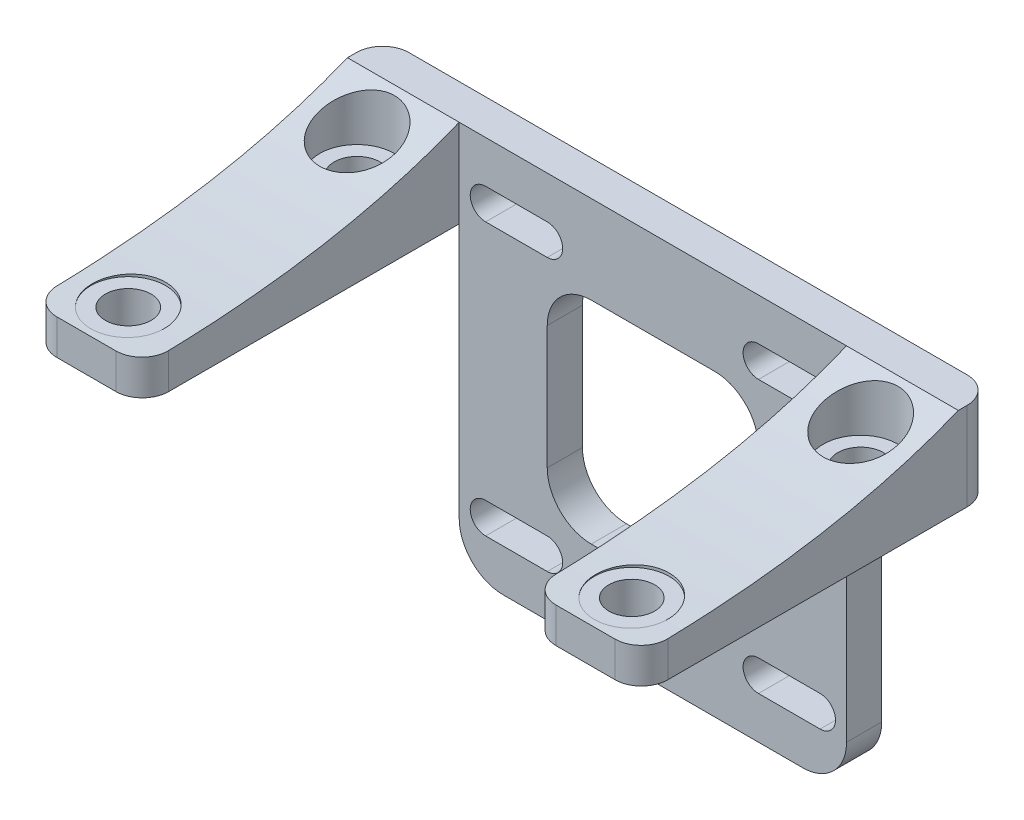
SolidWorks part; units mm, degrees
ref_plane "Front Plane" through (0, 0, 0) normal (0, 0, 1) x (1, 0, 0)
ref_plane "Top Plane" through (0, 0, 0) normal (0, 1, 0) x (1, 0, 0)
ref_plane "Right Plane" through (0, 0, 0) normal (1, 0, 0) x (0, 0, -1)
sketch "Sketch1" plane through (0, 0, 0) normal (0, 0, 1) x (1, 0, 0)
  line L0 (-19, 15.45) -> (-10.25, 15.45) construction
  line L1 (-22, 22) -> (22, 22)
  line L2 (-22, 22) -> (-22, -22)
  line L3 (-22, -22) -> (22, -22)
  line L4 (22, 22) -> (22, -22)
  line L5 (-22, 22) -> (22, -22) construction
  line L6 (-22, -22) -> (22, 22) construction
  line L7 (7, 12) -> (-7, 12)
  line L8 (12, 7) -> (12, -7)
  line L9 (7, -12) -> (-7, -12)
  line L10 (-12, 7) -> (-12, -7)
  line L11 (12, 12) -> (-12, -12) construction
  line L12 (12, -12) -> (-12, 12) construction
  line L13 (-19, 17.2) -> (-12, 17.2)
  line L14 (-19, 13.7) -> (-12, 13.7)
  line L15 (0, 0) -> (50000, 0) construction
  line L16 (-19, -17.2) -> (-12, -17.2)
  line L19 (12, 17.2) -> (19, 17.2)
  line L20 (12, 13.7) -> (19, 13.7)
  line L21 (10.25, 15.45) -> (19, 15.45) construction
  line L22 (-19, -13.7) -> (-12, -13.7)
  line L23 (12, -13.7) -> (19, -13.7)
  line L24 (12, -17.2) -> (19, -17.2)
  arc A0 (-12, -7) -> (-7, -12) centre (-7, -7) ccw
  arc A1 (7, -12) -> (12, -7) centre (7, -7) ccw
  arc A2 (12, 7) -> (7, 12) centre (7, 7) ccw
  arc A3 (-7, 12) -> (-12, 7) centre (-7, 7) ccw
  arc A4 (-19, 17.2) -> (-19, 13.7) centre (-19, 15.45) ccw
  arc A5 (19, 13.7) -> (19, 17.2) centre (19, 15.45) ccw
  circle A8 centre (0, 0) radius 12 construction
  arc A9 (12, 17.2) -> (12, 13.7) centre (12, 15.45) ccw
  arc A10 (-12, 17.2) -> (-12, 13.7) centre (-12, 15.45) cw
  arc A11 (-19, -17.2) -> (-19, -13.7) centre (-19, -15.45) cw
  arc A12 (-12, -17.2) -> (-12, -13.7) centre (-12, -15.45) ccw
  arc A13 (12, -17.2) -> (12, -13.7) centre (12, -15.45) cw
  arc A14 (19, -13.7) -> (19, -17.2) centre (19, -15.45) cw
  point P0 (0, 0)
  point P6 (0, 0)
  point P25 (0, 0)
  point P49 (0, 0)
  point P50 (0, 0)
  dimension "D4" = 5
  dimension "D9" = 1.75
  dimension "D1" = 44
  dimension "D2" = 44
  dimension "D3" = 24
  dimension "D5" = 38
  dimension "D6" = 1.75
  dimension "D7" = 15.45
  dimension "D8" = 7
extrude "Boss-Extrude1" add sketch "Sketch1" along normal blind 4
sketch "Sketch2" plane through (22, 0, 0) normal (1, 0, 0) x (0, 0, -1)
  line L0 (0, 12) -> (-40, 12)
  line L1 (0, -22) -> (0, 22) construction
  line L2 (0, 12) -> (0, 22)
  line L3 (0, 22) -> (-4, 22)
  line L4 (-40, 12) -> (-40, 16)
  line L5 (-40, 16) -> (0, 16) construction
  spline S0 degree 2 poles (-40, 16) (-18.3297, 16.1194) (-4, 22) knots 0 0 0 1 1 1
  dimension "D1" = 4
  dimension "D2" = 40
  dimension "D3" = 12
extrude "Boss-Extrude2" add sketch "Sketch2" along normal blind 12.7
sketch "Sketch3" plane through (0, 12, 0) normal (0, -1, 0) x (1, 0, 0)
  line L0 (34.7, 0) -> (22, 0) construction
  line L1 (34.7, 40) -> (34.7, 0) construction
  line L2 (34.7, 40) -> (22, 40) construction
  circle A0 centre (28.6, 35) radius 2.6
  circle A1 centre (28.6, 9) radius 2.6
  dimension "D2" = 5.2
  dimension "D1" = 6.1
  dimension "D3" = 5
  dimension "D4" = 9
extrude "Cut-Extrude1" cut sketch "Sketch3" against normal through all
ref_plane "Plane1" through (0, 16, 0) normal (0, -1, 0) x (-1, 0, 0)
sketch "Sketch4" plane through (0, 16, 0) normal (0, -1, 0) x (-1, 0, 0)
  circle A0 centre (-28.6, -9) radius 4.25
  circle A1 centre (-28.6, -35) radius 4.25
  dimension "D1" = 8.5
  dimension "D2" = 8.5
extrude "Cut-Extrude2" cut sketch "Sketch4" against normal through all
ref_plane "Plane2" through (0, 0, 0) normal (1, 0, 0) x (0, 0, -1)
mirror "Mirror1" about plane through (0, 0, 0) normal (1, 0, 0) of "Cut-Extrude1", "Cut-Extrude2", "Boss-Extrude2"
fillet "Fillet1" radius 3 6 edges at (34.7, 17, 0) (-34.7, 17, 0) (34.7, 14, 40) (22, 14, 40) (-22, 14, 40) (-34.7, 14, 40)
fillet "Fillet2" radius 5 2 edges at (22, -22, 2) (-22, -22, 2)
